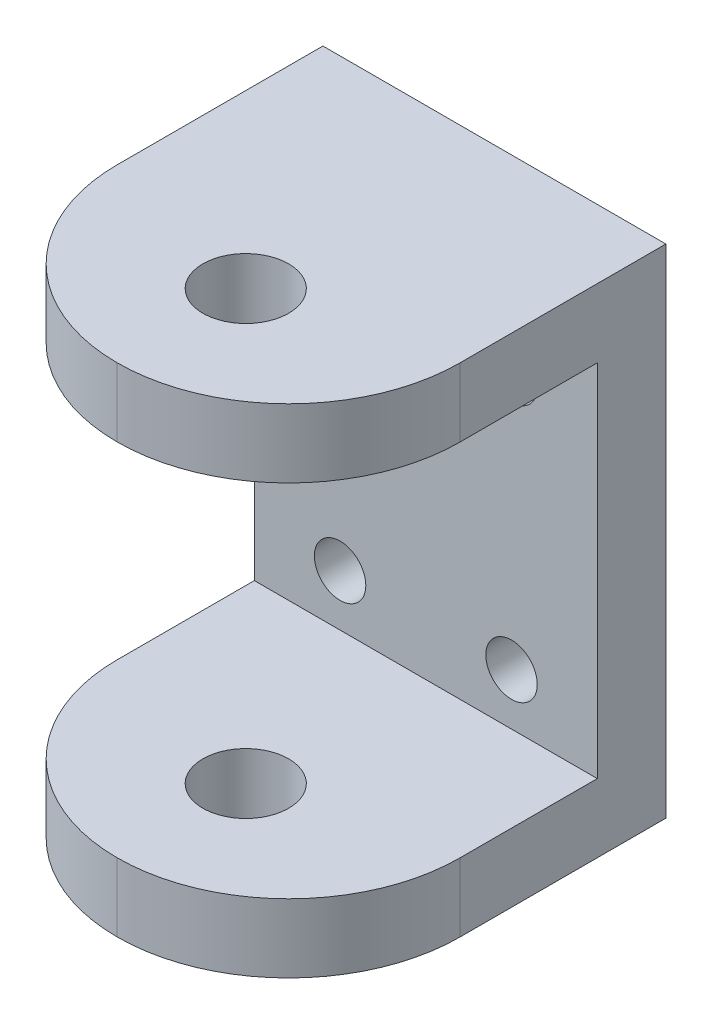
SolidWorks part; units mm, degrees
material "6061 合金"
ref_plane "前视基准面" through (0, 0, 0) normal (0, 0, 1) x (1, 0, 0)
ref_plane "上视基准面" through (0, 0, 0) normal (0, 1, 0) x (1, 0, 0)
ref_plane "右视基准面" through (0, 0, 0) normal (1, 0, 0) x (0, 0, -1)
sketch "草图1" plane through (0, 0, 0) normal (0, 0, 1) x (1, 0, 0)
  line L1 (-10, 14.5) -> (10, 14.5)
  line L2 (-10, 14.5) -> (-10, -14.5)
  line L3 (-10, -14.5) -> (10, -14.5)
  line L4 (10, 14.5) -> (10, -14.5)
  line L5 (-10, 14.5) -> (10, -14.5) construction
  line L6 (-10, -14.5) -> (10, 14.5) construction
  line L11 (-3.6206, 5.2499) -> (2.9548, -4.2845) construction
  line L12 (-3.1637, -4.6283) -> (3.3722, 4.9333) construction
  line L13 (-5, 7.5) -> (5, 7.5)
  line L14 (-5, 7.5) -> (-5, -7.5)
  line L15 (-5, -7.5) -> (5, -7.5)
  line L16 (5, 7.5) -> (5, -7.5)
  line L17 (-5, 7.5) -> (5, -7.5) construction
  line L18 (-5, -7.5) -> (5, 7.5) construction
  circle A0 centre (5, 7.5) radius 1.5
  circle A1 centre (-5, 7.5) radius 1.5
  circle A2 centre (-5, -7.5) radius 1.5
  circle A3 centre (5, -7.5) radius 1.5
  point P0 (0, 0)
  point P5 (0, 0)
  point P12 (0, 0)
  dimension "D6" = 3
  dimension "D7" = 3
  dimension "D8" = 3
  dimension "D9" = 3
  dimension "D1" = 29
  dimension "D2" = 20
  dimension "D3" = 15
  dimension "D4" = 7
  dimension "D5" = 10
extrude "凸台-拉伸1" add sketch "草图1" along normal blind 4 contours L4 L1 L2 L3 A3 L15 A2 L14 A1 L13 A0 L16 | A3 L16 A0 L13 A1 L14 A2 L15 region at (0, 14.1477, 0) region at (0, 0, 0)
sketch "草图2" plane through (0, 0, 4) normal (0, 0, 1) x (1, 0, 0)
  line L0 (10, 14.5) -> (10, -14.5) construction
  line L1 (-10, 14.5) -> (10, 14.5)
  line L2 (-10, 14.5) -> (-10, 10.5)
  line L3 (-10, 10.5) -> (10, 10.5)
  line L4 (10, 14.5) -> (10, 10.5)
  line L5 (-10, 14.5) -> (-10, -14.5) construction
  line L6 (10, -14.5) -> (-10, -14.5)
  line L7 (10, -14.5) -> (10, -10.5)
  line L8 (10, -10.5) -> (-10, -10.5)
  line L9 (-10, -14.5) -> (-10, -10.5)
  dimension "D1" = 4
  dimension "D2" = 4
extrude "凸台-拉伸2" add sketch "草图2" along normal blind 18
sketch "草图3" plane through (0, -14.5, 0) normal (0, -1, 0) x (1, 0, 0)
  line L0 (-10, 22) -> (-10, 0) construction
  line L1 (-10, 14.5) -> (10, 14.5)
  line L2 (10, 22) -> (10, 0) construction
  circle A0 centre (0, 14.5) radius 2.5
  point P0 (-10, 14.5)
  dimension "D2" = 5
  dimension "D1" = 14.5
extrude "切除-拉伸1" cut sketch "草图3" against normal through all contours L1 A0 | L1 A0 region at (0, -14.5, 15.561) region at (0, -14.5, 13.439)
fillet "圆角1" radius 10 4 edges at (10, -12.5, 22) (10, 12.5, 22) (-10, 12.5, 22) (-10, -12.5, 22)
